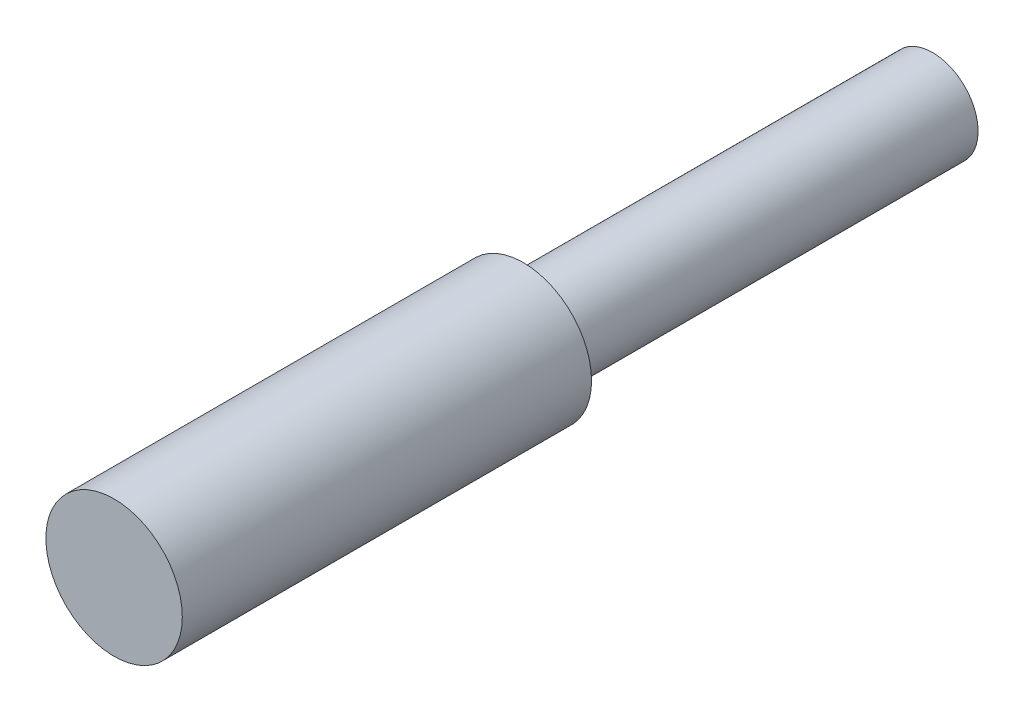
SolidWorks part; units mm, degrees
ref_plane "Front Plane" through (0, 0, 0) normal (0, 0, 1) x (1, 0, 0)
ref_plane "Top Plane" through (0, 0, 0) normal (0, 1, 0) x (1, 0, 0)
ref_plane "Right Plane" through (0, 0, 0) normal (1, 0, 0) x (0, 0, -1)
sketch "Sketch1" plane through (0, 0, 0) normal (0, 0, 1) x (1, 0, 0)
  circle A0 centre (0, 0) radius 3
  dimension "D1" = 6
extrude "Boss-Extrude1" add sketch "Sketch1" along normal blind 18 contours A0
sketch "Sketch2" plane through (0, 0, 0) normal (0, 0, -1) x (-1, 0, 0)
  circle A0 centre (0, 0) radius 2
  dimension "D1" = 4
extrude "Boss-Extrude2" add sketch "Sketch2" along normal blind 18
